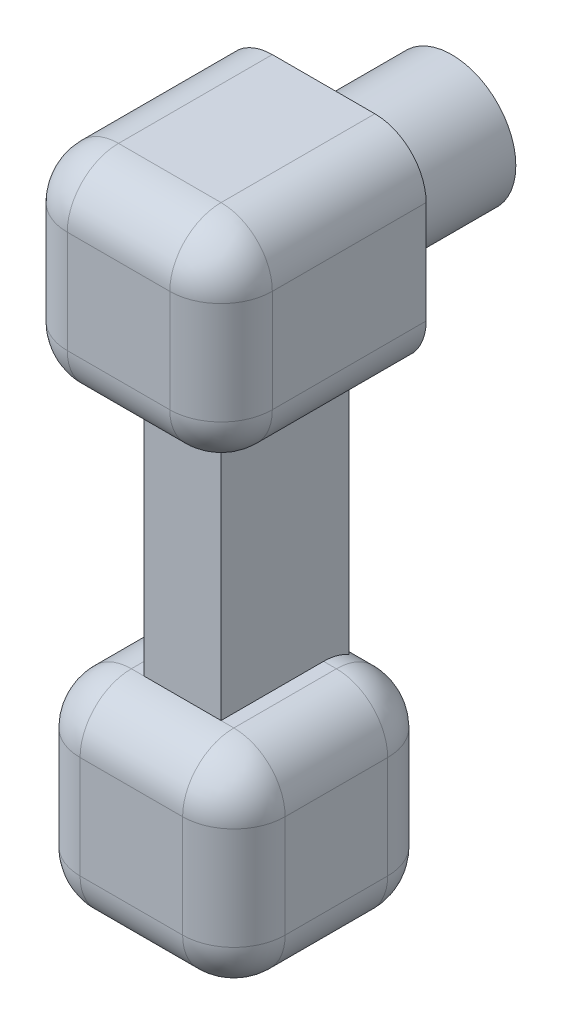
SolidWorks part; units mm, degrees
ref_plane "Plan de face" through (0, 0, 0) normal (0, 0, 1) x (1, 0, 0)
ref_plane "Plan de dessus" through (0, 0, 0) normal (0, 1, 0) x (1, 0, 0)
ref_plane "Plan de droite" through (0, 0, 0) normal (1, 0, 0) x (0, 0, -1)
sketch "Esquisse1" plane through (0, 0, 0) normal (0, 0, 1) x (1, 0, 0)
  circle A0 centre (0, 0) radius 12.5
  dimension "D1" = 25
extrude "Boss.-Extru.1" add sketch "Esquisse1" along normal blind 25
sketch "Esquisse2" plane through (0, 0, 25) normal (0, 0, 1) x (1, 0, 0)
  line L0 (0, 12.5) -> (0, -12.5) construction
  line L1 (-12.5, 0) -> (12.5, 0) construction
  line L3 (-10, 20) -> (10, 20)
  line L4 (-20, 10) -> (-20, -10)
  line L5 (-10, -20) -> (10, -20)
  line L6 (20, 10) -> (20, -10)
  line L7 (-20, 20) -> (20, -20) construction
  line L8 (-20, -20) -> (20, 20) construction
  circle A0 centre (0, 0) radius 12.5 construction
  arc A1 (-20, -10) -> (-10, -20) centre (-10, -10) ccw
  arc A2 (10, -20) -> (20, -10) centre (10, -10) ccw
  arc A3 (10, 20) -> (20, 10) centre (10, 10) cw
  arc A4 (-10, 20) -> (-20, 10) centre (-10, 10) ccw
  point P4 (0, 0)
  point P10 (0, 0)
  dimension "D3" = 10
  dimension "D1" = 40
  dimension "D2" = 40
extrude "Boss.-Extru.2" add sketch "Esquisse2" along normal blind 40
fillet "Congé1" radius 10 8 edges at (-20, 0, 65) (-17.0711, 17.0711, 65) (0, 20, 65) (17.0711, 17.0711, 65) (20, 0, 65) (17.0711, -17.0711, 65) (0, -20, 65) (-17.0711, -17.0711, 65)
sketch "Esquisse5" plane through (0, -20, 0) normal (0, -1, 0) x (1, 0, 0)
  line L0 (0, 0) -> (0, 55) construction
  line L1 (-10, 40) -> (10, 40) construction
  line L3 (-7.5, 52.5) -> (7.5, 52.5)
  line L4 (10, 25) -> (10, 55)
  line L5 (10, 55) -> (-10, 55)
  line L6 (-10, 55) -> (-10, 25)
  line L7 (-10, 25) -> (10, 25)
  line L8 (10, 25) -> (10, 55)
  line L9 (10, 55) -> (-10, 55)
  line L10 (-10, 55) -> (-10, 25)
  line L11 (-10, 25) -> (10, 25)
  line L12 (-7.5, 52.5) -> (-7.5, 27.5)
  line L13 (-7.5, 27.5) -> (7.5, 27.5)
  line L14 (7.5, 52.5) -> (7.5, 27.5)
  line L15 (-7.5, 52.5) -> (7.5, 27.5) construction
  line L16 (-7.5, 27.5) -> (7.5, 52.5) construction
  point P9 (0, 40)
  dimension "D2" = 25
  dimension "D3" = 15
  dimension "D1" = 0
extrude "Boss.-Extru.3" add sketch "Esquisse5" along normal blind 50 contours L12 L13 L14 L3
sketch "Esquisse6" plane through (0, 0, 27.5) normal (0, 0, -1) x (-1, 0, 0)
  line L0 (0, -70) -> (0, 0) construction
  line L1 (7.5, -70) -> (-7.5, -70) construction
  line L2 (-7.5, -70) -> (7.5, -70) construction
  line L4 (20, -70) -> (-20, -70)
  line L5 (20, -70) -> (20, -110)
  line L6 (20, -110) -> (-20, -110)
  line L7 (-20, -70) -> (-20, -110)
  dimension "D1" = 20
  dimension "D2" = 20
  dimension "D3" = 40
  dimension "D4" = 70
extrude "Boss.-Extru.4" add sketch "Esquisse6" along normal blind 5 and the other way blind 35
fillet "Congé2" radius 10 4 edges at (0, -110, 62.5) (20, -110, 42.5) (0, -110, 22.5) (-20, -110, 42.5)
fillet "Congé3" radius 10 8 edges at (17.0711, -107.0711, 25.4289) (17.0711, -107.0711, 59.5711) (-17.0711, -107.0711, 59.5711) (-17.0711, -107.0711, 25.4289) (20, -85, 22.5) (20, -85, 62.5) (-20, -85, 62.5) (-20, -85, 22.5)
sketch "Esquisse8" plane through (0, 0, 22.5) normal (0, 0, -1) x (-1, 0, 0)
  line L0 (0, -100) -> (0, 0) construction
  line L1 (-10, -100) -> (10, -100) construction
  line L2 (-10, -85) -> (10, -85) construction
  line L3 (-10, -70) -> (-10, -100) construction
  line L4 (10, -100) -> (10, -70) construction
  circle A0 centre (0, -85) radius 7.5
  dimension "D1" = 15
extrude "Enlèv. mat.-Extru.2" cut sketch "Esquisse8" against normal blind 20
fillet "Congé4" radius 10 8 edges at (-17.0711, -70, 59.5711) (0, -70, 62.5) (17.0711, -70, 59.5711) (20, -70, 42.5) (17.0711, -70, 25.4289) (0, -70, 22.5) (-17.0711, -70, 25.4289) (-20, -70, 42.5)
